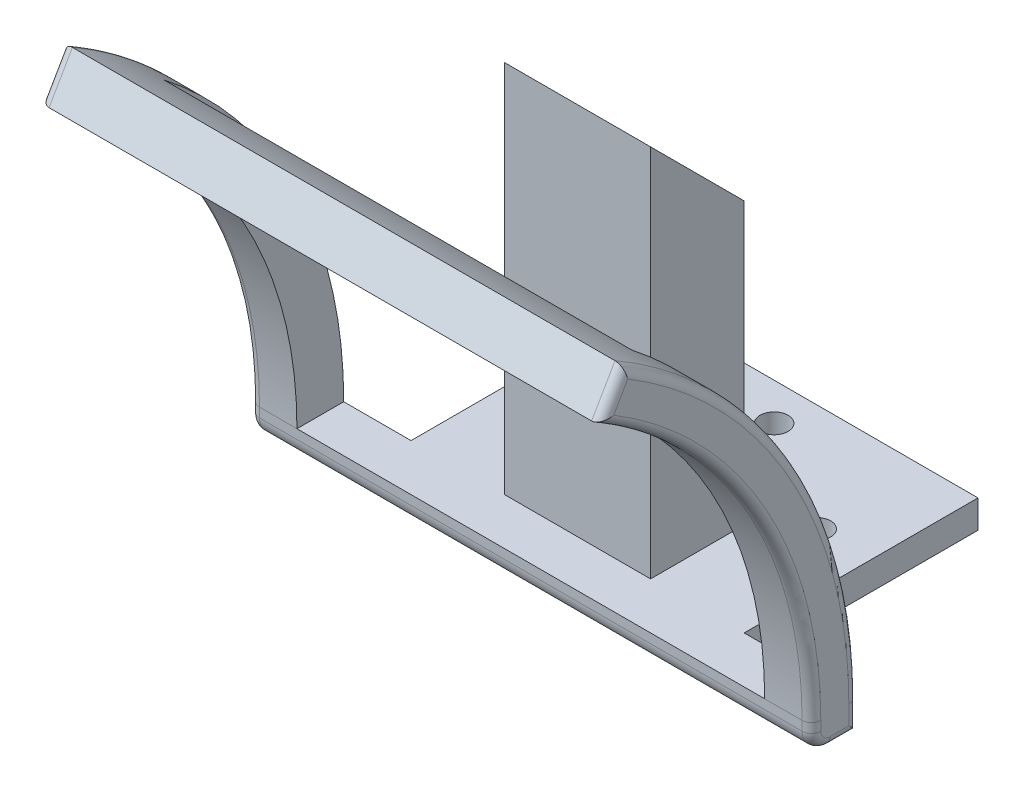
SolidWorks part; units mm, degrees
ref_plane "Front Plane" through (0, 0, 0) normal (0, 0, 1) x (1, 0, 0)
ref_plane "Top Plane" through (0, 0, 0) normal (0, 1, 0) x (1, 0, 0)
ref_plane "Right Plane" through (0, 0, 0) normal (1, 0, 0) x (0, 0, -1)
sketch "Sketch1" plane through (0, 0, 0) normal (0, 1, 0) x (1, 0, 0)
  line L0 (-8.4368, 20.25) -> (-8.4368, -4.75) construction
  line L1 (-26.2418, 20.25) -> (9.3682, 20.25)
  line L2 (-26.2418, 20.25) -> (-26.2418, -4.75)
  line L3 (-26.2418, -4.75) -> (9.3682, -4.75)
  line L4 (9.3682, 20.25) -> (9.3682, -4.75)
  line L5 (-38.4368, -4.75) -> (21.5632, -4.75)
  line L6 (-38.4368, -4.75) -> (-38.4368, -9.75)
  line L7 (-38.4368, -9.75) -> (21.5632, -9.75)
  line L8 (21.5632, -4.75) -> (21.5632, -9.75)
  point P10 (-8.4368, -4.75)
  dimension "D1" = 25
  dimension "D2" = 35.61
  dimension "D3" = 60
  dimension "D4" = 5
extrude "Boss-Extrude1" add sketch "Sketch1" along normal blind 3 contours L8 L5 L3 L6 L7 | L1 L0 L5 L4 | L0 L1 L2 L3 region at (0.4657, 0, -7.75) region at (-17.3393, 0, -7.75) region at (-8.4368, 0, 7.25)
fillet "Fillet1" radius 2 1 edges at (-8.4368, 0, 9.75)
ref_plane "Plane1" through (21.5632, 0, 0) normal (1, 0, 0) x (0, 0, -1)
sketch "Sketch2" plane through (21.5632, 0, 0) normal (1, 0, 0) x (0, 0, -1)
  line L0 (-9.75, 3) -> (-39.75, 3) construction
  line L1 (-39.75, 3) -> (-54.75, 3) construction
  line L2 (-29.75, 46.3013) -> (-32.25, 41.9711)
  line L3 (-9.75, 3) -> (-4.75, 3)
  circle A0 centre (-54.75, 3) radius 15 construction
  arc A1 (-9.75, 3) -> (-32.25, 41.9711) centre (-54.75, 3) ccw
  arc A2 (-4.75, 3) -> (-29.75, 46.3013) centre (-54.75, 3) ccw
  dimension "D3" = 30
  dimension "D1" = 30
  dimension "D2" = 15
extrude "Boss-Extrude3" add sketch "Sketch2" against normal blind 5
ref_plane "Plane2" through (-8.4368, 0, 0) normal (1, 0, 0) x (0, 0, -1)
mirror "Mirror3" about plane through (-8.4368, 0, 0) normal (1, 0, 0) of "Boss-Extrude3"
sketch "Sketch3" plane through (0, 0, 0) normal (0, -1, 0) x (1, 0, 0)
  circle A0 centre (-20.4847, -8.75) radius 1.5
  circle A1 centre (-8.4349, -16.25) radius 1.5
  circle A2 centre (3.6149, -8.75) radius 1.5
  dimension "D1" = 3
extrude "Cut-Extrude1" cut sketch "Sketch3" against normal blind 5
sketch "Sketch7" plane through (0, 3, 0) normal (0, 1, 0) x (1, 0, 0)
  line L0 (-26.2418, 20.25) -> (-26.2418, -4.75) construction
  line L1 (-16.2418, 5.25) -> (-0.6318, 5.25)
  line L2 (-16.2418, 5.25) -> (-16.2418, -4.75)
  line L3 (-16.2418, -4.75) -> (-0.6318, -4.75)
  line L4 (-0.6318, 5.25) -> (-0.6318, -4.75)
  line L5 (9.3682, 20.25) -> (9.3682, -4.75) construction
  line L6 (-38.4368, -9.75) -> (21.5632, -9.75) construction
  dimension "D1" = 10
  dimension "D2" = 10
  dimension "D3" = 5
  dimension "D4" = 10
extrude "Boss-Extrude4" add sketch "Sketch7" along normal blind 30
sketch "Sketch8" plane through (-16.2418, 0, 0) normal (-1, 0, 0) x (0, 0, 1)
  line L0 (-5.25, 33) -> (4.75, 43)
  line L1 (4.75, 33) -> (4.75, 43)
  line L2 (-5.25, 33) -> (4.75, 33) construction
  line L3 (-5.25, 33) -> (4.75, 33)
  dimension "D1" = 45
extrude "Boss-Extrude5" add sketch "Sketch8" against normal up to surface (15.61 mm away) up to face at (-0.6318, 18, -0.25)
sketch "Sketch9" plane through (0, 19.125, -19.125) normal (0, 0.7071, -0.7071) x (1, 0, 0)
  line L0 (-16.2418, -26.6933) -> (-0.6318, -26.6933) construction
  line L1 (-16.2418, -33.7643) -> (-16.2418, -19.6222) construction
  line L2 (-0.6318, -19.6222) -> (-0.6318, -33.7643) construction
  line L3 (-8.4368, -19.6222) -> (-8.4368, -33.7643) construction
  line L4 (-0.6318, -19.6222) -> (-16.2418, -19.6222) construction
  line L5 (-0.6318, -33.7643) -> (-16.2418, -33.7643) construction
  circle A0 centre (-11.4368, -26.6933) radius 1.5
  circle A1 centre (-5.4368, -26.6933) radius 1.5
  dimension "D1" = 3
  dimension "D2" = 3
  dimension "D3" = 6
  dimension "D4" = 3
extrude "Cut-Extrude2" cut sketch "Sketch9" against normal blind 5
sketch "Sketch10" plane through (-33.4368, 0, 0) normal (1, 0, 0) x (0, 0, -1)
  line L0 (-23.9669, 42.4005) -> (-27.0452, 38.4605)
  line L2 (-9.75, 3) -> (-4.75, 3)
  line L3 (-29.75, 46.3013) -> (-32.25, 41.9711)
  line L4 (-9.75, 3) -> (-4.75, 3)
  line L5 (-29.75, 46.3013) -> (-32.25, 41.9711)
  arc A2 (-9.75, 3) -> (-32.25, 41.9711) centre (-54.75, 3) ccw
  arc A3 (-4.75, 3) -> (-29.75, 46.3013) centre (-54.75, 3) ccw
  arc A4 (-9.75, 3) -> (-32.25, 41.9711) centre (-54.75, 3) ccw
  arc A5 (-4.75, 3) -> (-29.75, 46.3013) centre (-54.75, 3) ccw
  point P8 (-21.3431, 40.2018)
  arc M6 (-32.25, 41.9711) -> (-9.75, 3) centre (-54.75, 3) cw
  arc M8 (-4.75, 3) -> (-29.75, 46.3013) centre (-54.75, 3) ccw
  line M9 (-29.75, 46.3013) -> (-32.25, 41.9711)
  dimension "D2" = 8
  dimension "D1" = 0
extrude "Boss-Extrude6" add sketch "Sketch10" along normal up to surface (50 mm away) contours L0 M8 M9 M6 region at (-33.4368, 42.3836, 28.1854) up to face at (16.5632, 25.1591, 16.3694)
fillet "Fillet2" radius 1 14 edges at (-38.4368, 1.5, 4.75) (-38.4368, 28, 11.4487) (-38.4368, 44.1362, 31) (-38.4368, 25.5, 15.7789) (-38.4368, 2.5, 9.75) (-38.4368, 0.5858, 9.1642) (-38.4368, 0, 6.25) (21.5632, 25.5, 15.7789) (21.5632, 44.1362, 31) (21.5632, 28, 11.4487) (21.5632, 1.5, 4.75) (21.5632, 0, 6.25) (21.5632, 0.5858, 9.1642) (21.5632, 2.5, 9.75)
